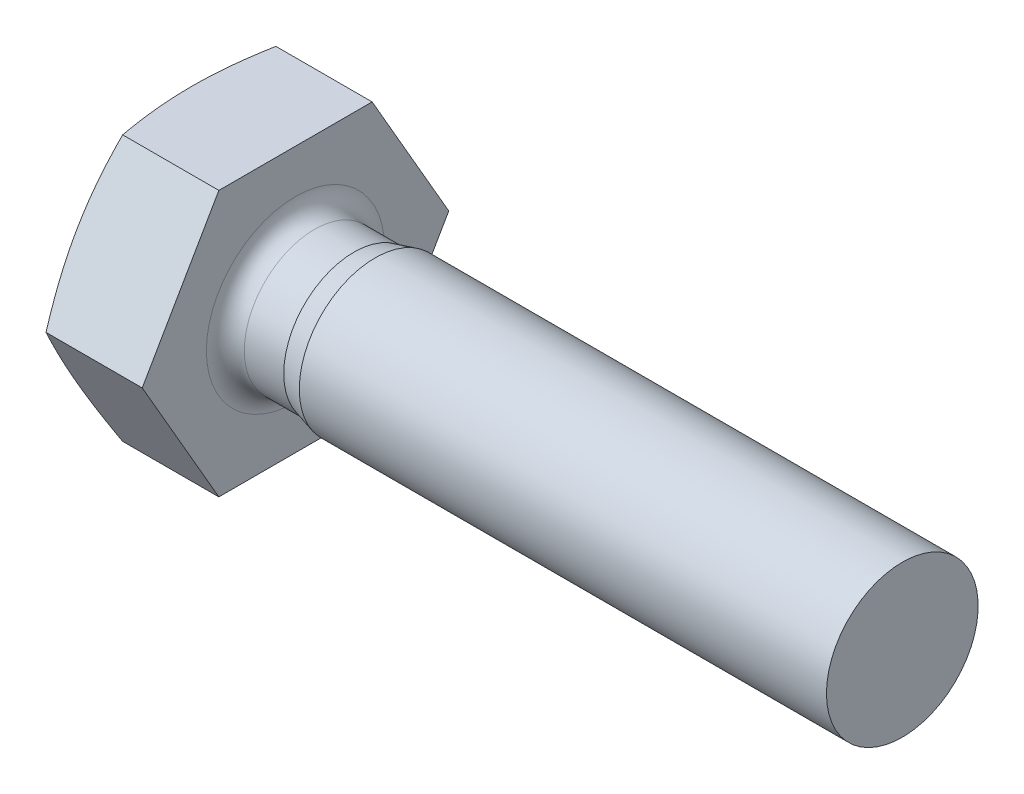
SolidWorks part; units mm, degrees
ref_plane "Front" through (0, 0, 0) normal (0, 0, 1) x (1, 0, 0)
ref_plane "Top" through (0, 0, 0) normal (0, 1, 0) x (1, 0, 0)
ref_plane "Right" through (0, 0, 0) normal (1, 0, 0) x (0, 0, -1)
sketch "Sketch2" plane through (0, 0, 0) normal (1, 0, 0) x (0, 0, -1)
  line L1 (2.0207, -3.5) -> (4.0415, 0)
  line L2 (4.0415, 0) -> (2.0207, 3.5)
  line L3 (2.0207, 3.5) -> (-2.0207, 3.5)
  line L4 (-2.0207, 3.5) -> (-4.0415, 0)
  line L5 (-4.0415, 0) -> (-2.0207, -3.5)
  line L6 (-2.0207, -3.5) -> (2.0207, -3.5)
  circle A0 centre (0, 0) radius 3.5 construction
  dimension "s" = 7
extrude "BaseHead" add sketch "Sketch2" along normal blind 2.8
sketch "Sketch10" plane through (0, 0, 0) normal (0, 1, 0) x (1, 0, 0)
  line L0 (0, 0) -> (15.3195, 0) construction
  line L1 (2.8, 2.35) -> (2.8, 0)
  line L2 (2.8, 0) -> (18.8, 0)
  line L3 (2.8, 2.0207) -> (2.8, -2.0207) construction
  line L4 (4.9, 2) -> (18.8, 2)
  line L5 (18.8, 0) -> (18.8, 2)
  line L6 (3.3, 1.85) -> (4.3402, 1.85)
  line L7 (2.8, 4.0415) -> (2.8, 2.0207) construction
  line L8 (4.9, 2) -> (4.3402, 1.85)
  line L9 (2.8, 4.0415) -> (2.8, 2.0207) construction
  arc A0 (2.8, 2.35) -> (3.3, 1.85) centre (3.3, 2.35) ccw
  dimension "r" = 0.5
  dimension "a" = 2.1
  dimension "l" = 16
  dimension "D1" = 15
revolve "Revolve1" add sketch "Sketch10" angle 360 about L0
cosmetic thread "ThreadCosmetic1" [suppressed] parameters "D2"=3
sketch "Sketch5" plane through (0, 0, 0) normal (0, 1, 0) x (1, 0, 0)
  line L0 (0, 4.0415) -> (0.2626, 4.0415)
  line L1 (0, 4.0415) -> (0, 2.0207) construction
  line L2 (0.2626, 4.0415) -> (0, 3.32)
  line L3 (2.8, 4.0415) -> (0, 4.0415) construction
  line L4 (0, 3.32) -> (0, 4.0415)
  line L5 (-0.3584, 0) -> (3.3946, 0) construction
  dimension "D2" = 20
revolve "HeadChamfer" cut sketch "Sketch5" angle 360 about L5
ref_plane "Plane1" through (1.8, 0, 0) normal (1, 0, 0) x (0, 0, -1)
sketch "Sketch6" plane through (0, 0, 0) normal (-1, 0, 0) x (0, 0, 1)
  circle A0 centre (0, 0) radius 3.32
  dimension "D1" = 6.64
extrude "Cut-Extrude1" cut sketch "Sketch6" against normal blind 1.8
sketch "Sketch7" plane through (0, 0, 0) normal (0, 1, 0) x (1, 0, 0)
  line L0 (1.8, 0) -> (6.7401, 0) construction
  line L1 (1.8, 3.32) -> (1.8, -3.32) construction
  line L2 (3.73, 0) -> (1.3, 2.5181)
  line L4 (1.3, 2.5181) -> (1.3, -2.5181)
  line L5 (1.3, -2.5181) -> (3.73, 0)
  line L7 (1.8, 2) -> (1.8, -2) construction
  dimension "D1" = 0.5
  dimension "h" = 1.93
extrude "Cut-Extrude2" cut sketch "Sketch7" against normal mid plane 0.772
pattern_circular "CirPattern2" count 2 every 90 about axis through (1.8, 0, 0) along (-1, 0, 0) of "Cut-Extrude2"
sketch "Sketch8" plane through (0, 0, 0) normal (0, 0, 1) x (1, 0, 0)
  line L0 (18.8, 1.567) -> (19.05, 2)
  line L1 (19.05, 2) -> (19.05, 2.5)
  line L2 (19.05, 2.5) -> (18.55, 2.5)
  line L3 (18.55, 2.5) -> (18.55, 2)
  line L4 (18.55, 2) -> (18.8, 1.567)
  line L5 (14.8, 0) -> (0, 0) construction
  line L6 (18.8, -2) -> (18.8, 2) construction
  line L7 (18.8, 2) -> (4.9, 2) construction
  dimension "D1" = 0.5
revolve "Cut-Revolve10" [suppressed] cut sketch "Sketch8" angle 360 about L5
pattern_linear "LPattern10" [suppressed] count 23 along (-1, 0, 0) of bodies 117
equation "\"D1@Sketch6\" = \"dw@Sketch5\""
equation "\"D1@Cut-Extrude1\" = \"k@BaseHead\" - \"k1@Plane1\""
equation "\"t@Cut-Extrude2\" = 0.4 * \"h@Sketch7\""
equation "\"D1@Sketch8\" =  ( \"d@Sketch10\" - \"D2@ThreadCosmetic1\" )  / 2"
equation "\"pitch@LPattern10\" = \"D1@Sketch8\" * 1.2"
equation "\"D1@LPattern10\" =  ( \"l@Sketch10\" - \"a@Sketch10\" )  / \"pitch@LPattern10\""
